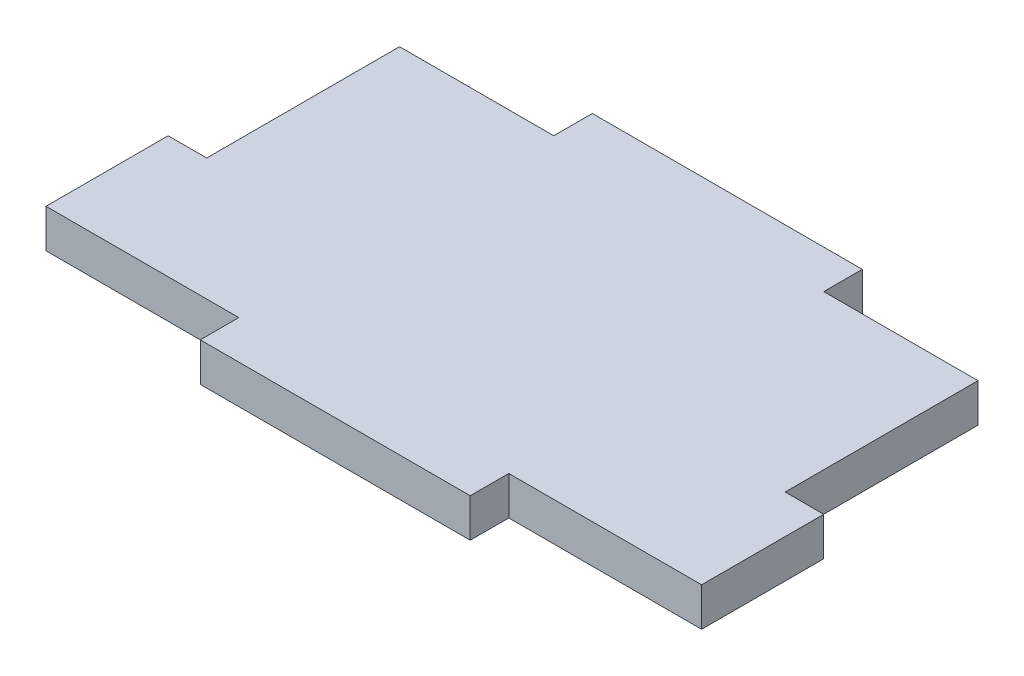
SolidWorks part; units mm, degrees
ref_plane "Front Plane" through (0, 0, 0) normal (0, 0, 1) x (1, 0, 0)
ref_plane "Top Plane" through (0, 0, 0) normal (0, 1, 0) x (1, 0, 0)
ref_plane "Right Plane" through (0, 0, 0) normal (1, 0, 0) x (0, 0, -1)
sketch "Sketch1" plane through (0, 0, 0) normal (0, 1, 0) x (1, 0, 0)
  line L1 (-50, -75) -> (50, -75)
  line L2 (-50, -75) -> (-50, 75)
  line L3 (-50, 75) -> (50, 75)
  line L4 (50, -75) -> (50, 75)
  line L5 (-50, -75) -> (50, 75) construction
  line L6 (-50, 75) -> (50, -75) construction
  point P0 (0, 0)
  dimension "D1" = 100
  dimension "D2" = 150
extrude "Boss-Extrude1" add sketch "Sketch1" along normal blind 150
sketch "Sketch13" plane through (50, 0, 0) normal (1, 0, 0) x (0, 0, -1)
  line L0 (-45, 40) -> (20, 0)
  line L1 (-75, 0) -> (-45, 0)
  line L2 (-75, 0) -> (-75, 40)
  line L3 (-75, 40) -> (-45, 40)
  line L5 (-75, 0) -> (75, 0) construction
  line L8 (-45, 0) -> (20, 0)
  dimension "D1" = 30
  dimension "D2" = 40
  dimension "D3" = 55
extrude "Cut-Extrude7" cut sketch "Sketch13" against normal up to next
shell "Shell1" thickness 6 removed face at (0, 150, 0)
sketch "Sketch3" plane through (0, 0, 0) normal (0, -1, 0) x (1, 0, 0)
  line L1 (50, 45) -> (50, 75) construction
  circle A0 centre (0, 60) radius 4
  circle A1 centre (-5, 50) radius 1.5
  circle A2 centre (5, 50) radius 1.5
  dimension "D3" = 8
  dimension "D4" = 3
  dimension "D5" = 10
  dimension "D7" = 10
  dimension "D8" = 5
  dimension "D1" = 60
  dimension "D2" = 50
extrude "Cut-Extrude2" cut sketch "Sketch3" against normal up to next
sketch "Sketch5" plane through (0, 0, 75) normal (0, 0, 1) x (1, 0, 0)
  line L0 (50, 150) -> (50, 40) construction
  line L1 (-25, 50) -> (25, 50)
  line L2 (-25, 50) -> (-25, 97)
  line L3 (-25, 97) -> (25, 97)
  line L4 (25, 50) -> (25, 97)
  line L5 (-25, 50) -> (25, 97) construction
  line L6 (-25, 97) -> (25, 50) construction
  line L7 (-50, 150) -> (50, 150) construction
  point P0 (0, 73.5)
  dimension "D1" = 50
  dimension "D2" = 47
  dimension "D3" = 50
  dimension "D4" = 76.5
extrude "Boss-Extrude3" add sketch "Sketch5" along normal blind 1
sketch "Sketch8" plane through (0, 0, 75) normal (0, 0, 1) x (1, 0, 0)
  line L0 (-50, 150) -> (-50, 40) construction
  line L1 (-25, 100) -> (25, 100)
  line L2 (-25, 100) -> (-25, 139)
  line L3 (-25, 139) -> (25, 139)
  line L4 (25, 100) -> (25, 139)
  line L5 (-25, 100) -> (25, 139) construction
  line L6 (-25, 139) -> (25, 100) construction
  line L7 (-50, 150) -> (50, 150) construction
  point P0 (0, 119.5)
  dimension "D1" = 50
  dimension "D2" = 39
  dimension "D3" = 50
  dimension "D4" = 50
extrude "Cut-Extrude3" cut sketch "Sketch8" against normal up to next
sketch "Sketch18" plane through (0, 0, 69) normal (0, 0, -1) x (-1, 0, 0)
  line L0 (-25, 139) -> (25, 139) construction
  line L1 (30, 99) -> (-26, 99)
  line L2 (30, 99) -> (30, 140)
  line L3 (30, 140) -> (-26, 140)
  line L4 (-26, 99) -> (-26, 140)
  line L6 (-25, 100) -> (-25, 139) construction
  line L7 (25, 139) -> (25, 100) construction
  dimension "D1" = 1
  dimension "D2" = 41
  dimension "D3" = 1
  dimension "D4" = 5
extrude "Cut-Extrude9" cut sketch "Sketch18" against normal blind 2
sketch "Sketch20" plane through (0, 0, 76) normal (0, 0, 1) x (1, 0, 0)
  line L0 (25, 97) -> (-25, 97) construction
  line L1 (-23, 96) -> (23, 96)
  line L2 (-23, 96) -> (-23, 51)
  line L3 (-23, 51) -> (23, 51)
  line L4 (23, 96) -> (23, 51)
  line L5 (-25, 50) -> (25, 50) construction
  line L6 (25, 50) -> (25, 97) construction
  line L7 (-25, 97) -> (-25, 50) construction
  dimension "D1" = 1
  dimension "D2" = 1
  dimension "D3" = 2
  dimension "D4" = 2
extrude "Cut-Extrude10" cut sketch "Sketch20" against normal blind 15 from offset 4 offset against normal yes
sketch "Sketch21" plane through (0, 46, 0) normal (0, 1, 0) x (1, 0, 0)
  line L1 (9, -52.5) -> (-9, -52.5)
  line L2 (9, -52.5) -> (9, -37.5)
  line L3 (9, -37.5) -> (-9, -37.5)
  line L4 (-9, -52.5) -> (-9, -37.5)
  circle A0 centre (5, -50) radius 1.5 construction
  circle A1 centre (-5, -50) radius 1.5 construction
  dimension "D3" = 4
  dimension "D1" = 4
  dimension "D2" = 2.5
  dimension "D4" = 15
extrude "Cut-Extrude11" cut sketch "Sketch21" against normal blind 2.5
sketch "Sketch22" plane through (-44, 0, 0) normal (1, 0, 0) x (0, 0, -1)
  line L0 (69, 150) -> (-69, 150) construction
  line L5 (69, 150) -> (69, 6) construction
  line L7 (-43.3017, 46) -> (21.6983, 6) construction
  line L8 (9, 150) -> (9, 13.8143)
  line L11 (9, 150) -> (4, 150)
  line L14 (4, 150) -> (4, 16.8912)
  line L15 (4, 16.8912) -> (9, 13.8143)
  dimension "D1" = 60
  dimension "D3" = 5
extrude "Boss-Extrude6" add sketch "Sketch22" along normal blind 5
mirror "Mirror2" about plane through (0, 0, 0) normal (1, 0, 0) of "Boss-Extrude6"
sketch "Sketch23" plane through (-44, 0, 0) normal (1, 0, 0) x (0, 0, -1)
  line L0 (15, 150) -> (20, 150)
  line L1 (69, 150) -> (9, 150) construction
  line L3 (20, 150) -> (20, 7.0451)
  line L4 (20, 7.0451) -> (15, 10.122)
  line L6 (9, 13.8143) -> (9, 150) construction
  line L7 (15, 150) -> (15, 10.122)
  line L8 (9, 13.8143) -> (21.6983, 6) construction
  dimension "D1" = 6
  dimension "D2" = 5
extrude "Boss-Extrude7" add sketch "Sketch23" along normal up to next
sketch "Sketch24" plane through (-44, 0, 0) normal (1, 0, 0) x (0, 0, -1)
  line L0 (69, 150) -> (69, 6) construction
  line L1 (69, 135) -> (66, 135)
  line L2 (69, 135) -> (69, 105)
  line L3 (69, 105) -> (66, 105)
  line L4 (66, 135) -> (66, 105)
  line L5 (69, 150) -> (20, 150) construction
  line L6 (69, 6) -> (21.6983, 6) construction
  line L7 (69, 21) -> (66, 21)
  line L8 (69, 21) -> (69, 51)
  line L9 (69, 51) -> (66, 51)
  line L10 (66, 21) -> (66, 51)
  dimension "D1" = 15
  dimension "D2" = 30
  dimension "D3" = 3
  dimension "D4" = 15
extrude "Cut-Extrude12" cut sketch "Sketch24" against normal through all both and the other way through all
sketch "Sketch28" plane through (0, 0, 76) normal (0, 0, 1) x (1, 0, 0)
  line L0 (-25, 73.5) -> (25, 73.5) construction
  line L1 (-25, 97) -> (-25, 50) construction
  line L2 (25, 50) -> (25, 97) construction
  line L3 (-25, 77.511) -> (25, 77.511) construction
  text T0 "SCAN\r\nHERE" font "Impact" height 10
extrude "Cut-Extrude14" cut sketch "Sketch28" against normal blind 1
sketch "Sketch30" plane through (0, 0, -75) normal (0, 0, -1) x (-1, 0, 0)
  text T0 "IBE VAN DE VEIRE\r\nSTEF GIELEN" font "Comic Sans MS" height 5
extrude "Cut-Extrude16" cut sketch "Sketch30" against normal blind 1
sketch "Sketch32" plane through (0, 150, 0) normal (0, 1, 0) x (1, 0, 0)
  line L0 (-50, 75) -> (-50, -75) construction
  line L1 (50, 75) -> (-50, 75) construction
  line L2 (-50, -75) -> (50, -75) construction
  line L3 (50, -75) -> (50, 75) construction
  circle A0 centre (-47, 72) radius 1.225
  circle A1 centre (-47, -72) radius 1.225
  circle A2 centre (47, -72) radius 1.225
  circle A3 centre (47, 72) radius 1.225
  dimension "D1" = 2.45
  dimension "D2" = 3
  dimension "D3" = 3
  dimension "D4" = 2.45
  dimension "D5" = 3
  dimension "D6" = 3
  dimension "D7" = 2.45
  dimension "D8" = 3
  dimension "D9" = 3
  dimension "D10" = 2.45
  dimension "D11" = 3
  dimension "D12" = 3
extrude "Cut-Extrude17" cut sketch "Sketch32" against normal blind 20
sketch "Sketch33" plane through (0, 150, 0) normal (0, 1, 0) x (1, 0, 0)
  line L1 (-44, 4) -> (44, 4)
  line L2 (-44, 4) -> (-44, 20)
  line L3 (-44, 20) -> (44, 20)
  line L4 (44, 4) -> (44, 20)
extrude "Cut-Extrude18" cut sketch "Sketch33" against normal blind 40
sketch "Sketch34" plane through (0, 150, 0) normal (0, 1, 0) x (1, 0, 0)
  line L0 (50, 75) -> (-50, 75) construction
  line L1 (-45, 75) -> (50, 75)
  line L2 (-45, 75) -> (-45, -75)
  line L3 (-45, -75) -> (50, -75)
  line L4 (50, 75) -> (50, -75)
sketch "Sketch35" plane through (-50, 0, 0) normal (-1, 0, 0) x (0, 0, 1)
  line L0 (-75, 150) -> (-75, 0) construction
  line L1 (-75, 5) -> (253.085, 5)
  line L2 (-75, 5) -> (-75, 218.2416)
  line L3 (-75, 218.2416) -> (253.085, 218.2416)
  line L4 (253.085, 5) -> (253.085, 218.2416)
  line L5 (-75, 0) -> (-20, 0) construction
  dimension "D1" = 5
extrude "Cut-Extrude19" cut sketch "Sketch35" against normal through all both and the other way through all
sketch "Sketch36" plane through (-50, 0, 0) normal (-1, 0, 0) x (0, 0, 1)
  line L0 (-75, 0) -> (-20, 0) construction
  line L1 (-20, 0) -> (10.0698, 0)
  line L2 (-20, 0) -> (-20, 13.8237)
  line L3 (-20, 13.8237) -> (10.0698, 13.8237)
  line L4 (10.0698, 0) -> (10.0698, 13.8237)
  line L5 (-11.875, 5) -> (-20, 0) construction
extrude "Cut-Extrude20" cut sketch "Sketch36" against normal through all both and the other way through all
sketch "Sketch37" plane through (0, 5, 0) normal (0, 1, 0) x (1, 0, 0)
  line L1 (-50, 75) -> (50, 75)
  line L2 (-50, 75) -> (-50, 20)
  line L3 (-50, 20) -> (50, 20)
  line L4 (50, 75) -> (50, 20)
extrude "Boss-Extrude8" add sketch "Sketch37" along normal blind 1
sketch "Sketch38" plane through (50, 0, 0) normal (1, 0, 0) x (0, 0, -1)
  line L0 (20, 6) -> (75, 6) construction
  line L1 (20, 6) -> (75, 6)
  line L2 (20, 6) -> (20, 0)
  line L3 (20, 0) -> (75, 0)
  line L4 (75, 6) -> (75, 0)
  line L5 (20, 6) -> (20, 0) construction
  line L6 (75, 6) -> (75, 0) construction
  line L7 (20, 0) -> (75, 0) construction
extrude "Boss-Extrude9" add sketch "Sketch38" along normal blind 2
sketch "Sketch40" plane through (0, 0, -75) normal (0, 0, -1) x (-1, 0, 0)
  line L0 (-52, 0) -> (-52, 36) construction
  line L1 (-52, 6) -> (-22, 6)
  line L2 (-52, 6) -> (-52, 0)
  line L3 (-52, 0) -> (-22, 0)
  line L4 (-22, 6) -> (-22, 0)
  line L5 (-52, 0) -> (-52, 6) construction
  line L6 (-52, 0) -> (50, 0) construction
  line L7 (-52, 6) -> (50, 6) construction
  line L8 (50, 0) -> (20, 0)
  line L9 (50, 0) -> (50, 6)
  line L10 (50, 6) -> (20, 6)
  line L11 (20, 0) -> (20, 6)
  dimension "D1" = 30
  dimension "D2" = 30
extrude "Cut-Extrude21" cut sketch "Sketch40" against normal blind 6
ref_plane "Plane1" through (0, 0, -44.5) normal (0, 0, -1) x (-1, 0, 0)
ref_plane "Plane2" through (0, 0, -44.5) normal (0, 0, -1) x (-1, 0, 0)
sketch "Sketch41" plane through (0, 0, -20) normal (0, 0, 1) x (1, 0, 0)
  line L0 (-50, 0) -> (52, 0) construction
  line L1 (-20, 0) -> (22, 0)
  line L2 (-20, 0) -> (-20, 6)
  line L3 (-20, 6) -> (22, 6)
  line L4 (22, 0) -> (22, 6)
  line L5 (-50, 6) -> (52, 6) construction
  line L6 (-50, 0) -> (-50, 6) construction
  line L7 (52, 6) -> (52, 0) construction
  dimension "D1" = 30
  dimension "D2" = 30
extrude "Boss-Extrude10" add sketch "Sketch41" along normal blind 6
sketch "Sketch42" plane through (52, 0, 0) normal (1, 0, 0) x (0, 0, -1)
  line L0 (69, 6) -> (20, 6) construction
  line L1 (69, 0) -> (39, 0)
  line L2 (69, 0) -> (69, 6)
  line L3 (69, 6) -> (39, 6)
  line L4 (39, 0) -> (39, 6)
  dimension "D1" = 30
extrude "Cut-Extrude22" cut sketch "Sketch42" against normal blind 6
ref_plane "Plane3" through (1, 0, 0) normal (1, 0, 0) x (0, 0, -1)
mirror "Mirror5" about plane through (1, 0, 0) normal (1, 0, 0) of "Cut-Extrude22"
